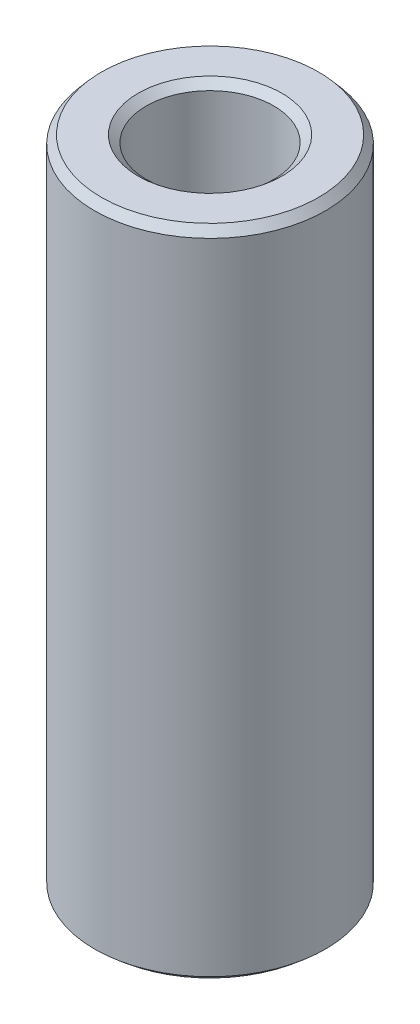
SolidWorks part; units mm, degrees
ref_plane "Front Plane" through (0, 0, 0) normal (0, 0, 1) x (1, 0, 0)
ref_plane "Top Plane" through (0, 0, 0) normal (0, 1, 0) x (1, 0, 0)
ref_plane "Right Plane" through (0, 0, 0) normal (1, 0, 0) x (0, 0, -1)
sketch "Sketch1" plane through (0, 0, 0) normal (0, 1, 0) x (1, 0, 0)
  circle A0 centre (0, 0) radius 42.5
  dimension "SLEEVE_OD" = 85
extrude "Boss-Extrude1" add sketch "Sketch1" along normal blind 240.747
sketch "Sketch2" plane through (0, 0, 0) normal (0, 1, 0) x (1, 0, 0)
  circle A0 centre (0, 0) radius 23.4475
  dimension "BORE_D" = 46.8951
extrude "Cut-Extrude1" cut sketch "Sketch2" along normal through all
chamfer "Chamfer1" distance 2.9979 angle 40.303 4 edges at (0, 240.747, 23.4475) (0, 0, 23.4475) (0, 0, 42.5) (0, 240.747, 42.5) first distance on face at (0, 240.747, 23.4475) first distance on face at (0, 0, 23.4475) first distance on face at (0, 240.747, 42.5)
